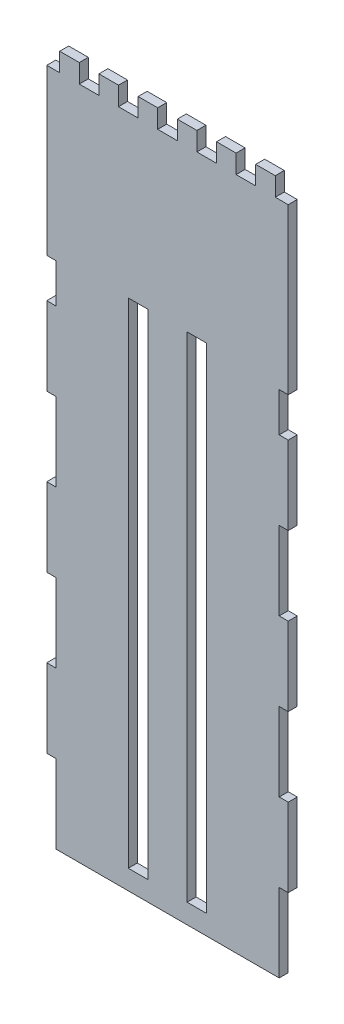
SolidWorks part; units mm, degrees
ref_plane "Front Plane" through (0, 0, 0) normal (0, 0, 1) x (1, 0, 0)
ref_plane "Top Plane" through (0, 0, 0) normal (0, 1, 0) x (1, 0, 0)
ref_plane "Right Plane" through (0, 0, 0) normal (1, 0, 0) x (0, 0, -1)
sketch "Sketch1" plane through (0, 0, 0) normal (0, 0, 1) x (1, 0, 0)
  line L1 (-39.116, 109.22) -> (39.116, 109.22)
  line L2 (-39.116, 109.22) -> (-39.116, -109.22)
  line L3 (-39.116, -109.22) -> (39.116, -109.22)
  line L4 (39.116, 109.22) -> (39.116, -109.22)
  point P4 (0, 109.22)
  point P7 (-39.116, 0)
  dimension "D1" = 78.232
  dimension "D2" = 218.44
extrude "Boss-Extrude1" add sketch "Sketch1" along normal mid plane 2.921
sketch "Sketch2" plane through (0, 0, 1.4605) normal (0, 0, 1) x (1, 0, 0)
  line L0 (-36.195, -109.22) -> (36.195, -109.22)
  line L1 (-39.116, 109.22) -> (39.116, 109.22)
  line L2 (-39.116, 109.22) -> (-39.116, -109.22)
  line L3 (-39.116, -109.22) -> (-36.195, -109.22)
  line L4 (39.116, 109.22) -> (39.116, -109.22)
  line L5 (-39.116, 109.22) -> (-36.195, 109.22)
  line L6 (-39.116, 109.22) -> (-39.116, -109.22)
  line L7 (-39.116, -109.22) -> (-36.195, -109.22)
  line L8 (-36.195, 109.22) -> (-36.195, -109.22)
  line L9 (39.116, -109.22) -> (36.195, -109.22)
  line L10 (39.116, -109.22) -> (39.116, 109.22)
  line L11 (39.116, 109.22) -> (36.195, 109.22)
  line L12 (36.195, -109.22) -> (36.195, 109.22)
  line L13 (36.195, -109.22) -> (39.116, -109.22)
  line L14 (-39.116, -83.82) -> (-36.195, -83.82)
  line L15 (39.116, -83.82) -> (36.195, -83.82)
  line L16 (-39.116, -58.42) -> (-36.195, -58.42)
  line L17 (39.116, -58.42) -> (36.195, -58.42)
  line L18 (-39.116, -33.02) -> (-36.195, -33.02)
  line L19 (39.116, -33.02) -> (36.195, -33.02)
  line L20 (-39.116, -7.62) -> (-36.195, -7.62)
  line L21 (39.116, -7.62) -> (36.195, -7.62)
  line L22 (-39.116, 17.78) -> (-36.195, 17.78)
  line L23 (39.116, 17.78) -> (36.195, 17.78)
  line L24 (-39.116, 43.18) -> (-36.195, 43.18)
  line L25 (39.116, 43.18) -> (36.195, 43.18)
  line L26 (-39.116, -109.22) -> (-39.116, -83.82) construction
  line L27 (-39.116, 55.88) -> (39.116, 55.88)
  point P40 (-37.6555, 43.18)
  line M28 (-39.116, -109.22) -> (39.116, -109.22)
  line M29 (39.116, -109.22) -> (39.116, 109.22)
  dimension "D1" = 2.921
  dimension "D2" = 2.921
  dimension "D4" = 25.4
  dimension "D5" = 2.921
  dimension "D6" = 12.7
  dimension "D3" = 7
extrude "Cut-Extrude1" cut sketch "Sketch2" against normal blind 2.921 contours L14 L6 L8 M28 | L18 L6 L16 L8 | L22 L6 L20 L8 | L27 L6 L24 L8 | L27 L12 L25 M29 | L23 L12 L21 M29 | L15 L12 M29 M28 | L19 L12 L17 M29 region at (-37.6555, -96.52, 1.4605) region at (37.6555, -96.52, 1.4605) region at (-37.6555, -45.72, 1.4605) region at (37.6555, -45.72, 1.4605) region at (-37.6555, 5.08, 1.4605) region at (37.6555, 5.08, 1.4605) region at (-37.6555, 49.53, 1.4605) region at (37.6555, 49.53, 1.4605)
sketch "Sketch3" plane through (0, 109.22, 0) normal (0, 1, 0) x (1, 0, 0)
  line L0 (39.116, 1.4605) -> (-39.116, 1.4605) construction
  line L1 (34.925, 1.4605) -> (28.575, 1.4605)
  line L2 (34.925, 1.4605) -> (34.925, -1.4605)
  line L3 (34.925, -1.4605) -> (28.575, -1.4605)
  line L4 (28.575, 1.4605) -> (28.575, -1.4605)
  line L5 (39.116, -1.4605) -> (-39.116, -1.4605) construction
  line L6 (39.116, -1.4605) -> (39.116, 1.4605) construction
  line L7 (22.225, 1.4605) -> (22.225, -1.4605)
  line L8 (22.225, 1.4605) -> (15.875, 1.4605)
  line L9 (15.875, 1.4605) -> (15.875, -1.4605)
  line L10 (22.225, -1.4605) -> (15.875, -1.4605)
  line L11 (9.525, 1.4605) -> (9.525, -1.4605)
  line L12 (9.525, 1.4605) -> (3.175, 1.4605)
  line L13 (3.175, 1.4605) -> (3.175, -1.4605)
  line L14 (9.525, -1.4605) -> (3.175, -1.4605)
  line L15 (-3.175, 1.4605) -> (-3.175, -1.4605)
  line L16 (-3.175, 1.4605) -> (-9.525, 1.4605)
  line L17 (-9.525, 1.4605) -> (-9.525, -1.4605)
  line L18 (-3.175, -1.4605) -> (-9.525, -1.4605)
  line L19 (-15.875, 1.4605) -> (-15.875, -1.4605)
  line L20 (-15.875, 1.4605) -> (-22.225, 1.4605)
  line L21 (-22.225, 1.4605) -> (-22.225, -1.4605)
  line L22 (-15.875, -1.4605) -> (-22.225, -1.4605)
  line L23 (-28.575, 1.4605) -> (-28.575, -1.4605)
  line L24 (-28.575, 1.4605) -> (-34.925, 1.4605)
  line L25 (-34.925, 1.4605) -> (-34.925, -1.4605)
  line L26 (-28.575, -1.4605) -> (-34.925, -1.4605)
  line L27 (34.925, 1.4605) -> (22.225, 1.4605) construction
  point P10 (28.575, 0)
  dimension "D1" = 4.191
  dimension "D2" = 6.35
  dimension "D4" = 12.7
  dimension "D3" = 6
extrude "Boss-Extrude2" add sketch "Sketch3" along normal blind 6.0452
sketch "Sketch5" plane through (0, 0, 1.4605) normal (0, 0, 1) x (1, 0, 0)
  line L0 (0, 109.22) -> (0, -109.22) construction
  line L1 (-12.7, 57.15) -> (-6.35, 57.15)
  line L2 (-12.7, 57.15) -> (-12.7, -102.87)
  line L3 (-12.7, -102.87) -> (-6.35, -102.87)
  line L4 (-6.35, 57.15) -> (-6.35, -102.87)
  line L5 (6.35, 57.15) -> (12.7, 57.15)
  line L6 (6.35, 57.15) -> (6.35, -102.87)
  line L7 (6.35, -102.87) -> (12.7, -102.87)
  line L8 (12.7, 57.15) -> (12.7, -102.87)
  line L9 (3.175, 109.22) -> (-3.175, 109.22) construction
  line L10 (-36.195, -109.22) -> (36.195, -109.22) construction
  line L11 (-9.525, 109.22) -> (-15.875, 109.22) construction
  line L12 (-6.35, 57.15) -> (6.35, 57.15) construction
  point P16 (0, 57.15)
  dimension "D1" = 25.4
  dimension "D2" = 52.07
  dimension "D3" = 6.35
  dimension "D4" = 6.35
extrude "Cut-Extrude2" cut sketch "Sketch5" against normal through all
